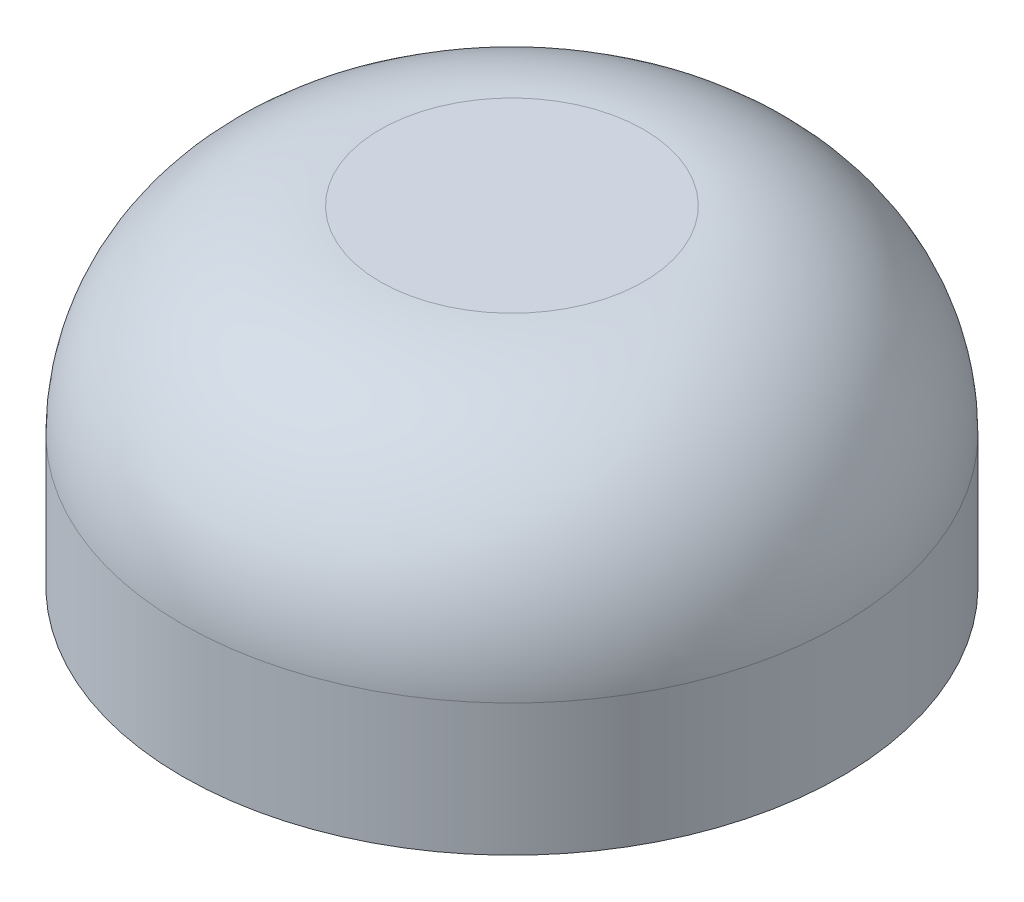
SolidWorks part; units mm, degrees
material "ABS"
ref_plane "Front Plane" through (0, 0, 0) normal (0, 0, 1) x (1, 0, 0)
ref_plane "Top Plane" through (0, 0, 0) normal (0, 1, 0) x (1, 0, 0)
ref_plane "Right Plane" through (0, 0, 0) normal (1, 0, 0) x (0, 0, -1)
sketch "Sketch1" plane through (0, 0, 0) normal (0, 1, 0) x (1, 0, 0)
  circle A0 centre (0, 0) radius 10
  dimension "D1" = 20
extrude "Boss-Extrude1" add sketch "Sketch1" along normal blind 10
fillet "Fillet1" radius 6 1 edges at (0, 10, 10)
